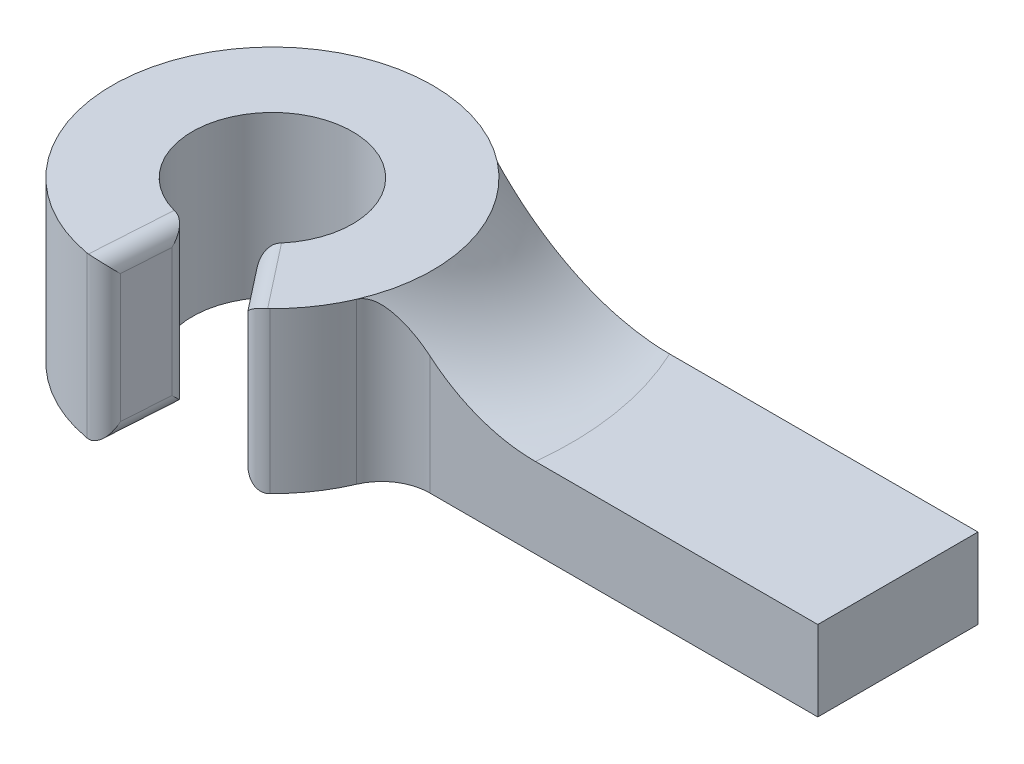
SolidWorks part; units mm, degrees
ref_plane "Front Plane" through (0, 0, 0) normal (0, 0, 1) x (1, 0, 0)
ref_plane "Top Plane" through (0, 0, 0) normal (0, 1, 0) x (1, 0, 0)
ref_plane "Right Plane" through (0, 0, 0) normal (1, 0, 0) x (0, 0, -1)
sketch "Sketch1" plane through (0, 0, 0) normal (0, 1, 0) x (1, 0, 0)
  line L0 (-0.314, -4.9901) -> (-0.6281, -9.9803)
  line L6 (6.1647, -7.8737) -> (3.0824, -3.9369)
  line L11 (6.1647, 7.8737) -> (26.1647, 7.8737)
  line L12 (6.1647, 7.8737) -> (6.1647, -2.1263)
  line L13 (6.1647, -2.1263) -> (26.1647, -2.1263)
  line L14 (26.1647, 7.8737) -> (26.1647, -2.1263)
  arc A0 (6.1647, -7.8737) -> (-0.6281, -9.9803) centre (0, 0) ccw
  arc A1 (3.0824, -3.9369) -> (-0.314, -4.9901) centre (0, 0) ccw
  dimension "D1" = 10
  dimension "D2" = 5
  dimension "D3" = 20
  dimension "D4" = 10
extrude "Boss-Extrude1" add sketch "Sketch1" along normal blind 5 contours A0 L13 L14 L11 region at (17.5837, 0, -3.0361)
extrude "Boss-Extrude2" add sketch "Sketch1<3>" along normal blind 10 contours L13 A0 L12 | A1 L6 A0 L13 L12 L0 region at (-0.7516, 0, 7.4675) region at (7.8147, 0, -1.9184)
sketch "Sketch1<3>" plane through (0, 0, 0) normal (0, 1, 0) x (1, 0, 0) same geometry as "Sketch1"
fillet "Fillet1" radius 10 1 edges at (9.4069, 5, -3.3927)
fillet "Fillet2" radius 3 1 edges at (9.7713, 5, 2.1263)
fillet "Fillet3" radius 1 8 edges at (4.6236, 0, 5.9053) (4.6236, 10, 5.9053) (-0.4711, 0, 7.4852) (-0.4711, 10, 7.4852) (6.1647, 5, 7.8737) (3.0824, 5, 3.9369) (-0.6281, 5, 9.9803) (-0.314, 5, 4.9901)
ref_plane "Plane1" through (26.1647, 0, 0) normal (1, 0, 0) x (0, 0, -1)
sketch "Sketch2" plane through (26.1647, 0, 0) normal (1, 0, 0) x (0, 0, -1)
  line L1 (7.8737, 5) -> (-2.1263, 5)
  line L2 (7.8737, 5) -> (7.8737, 0)
  line L3 (7.8737, 0) -> (-2.1263, 0)
  line L4 (-2.1263, 5) -> (-2.1263, 0)
extrude "Boss-Extrude3" add sketch "Sketch2" along normal blind 10
